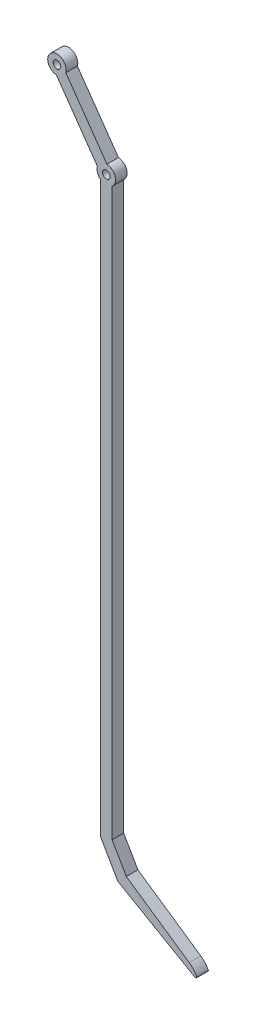
SolidWorks part; units mm, degrees
ref_plane "前视基准面" through (0, 0, 0) normal (0, 0, 1) x (1, 0, 0)
ref_plane "上视基准面" through (0, 0, 0) normal (0, 1, 0) x (1, 0, 0)
ref_plane "右视基准面" through (0, 0, 0) normal (1, 0, 0) x (0, 0, -1)
sketch "草图1" plane through (0, 0, 0) normal (0, 0, 1) x (1, 0, 0)
  line L0 (-2.5, -125) -> (5, -137.9904)
  line L1 (-2.5, 125) -> (2.5, 125) construction
  line L2 (-2.5, 125) -> (-2.5, -125) construction
  line L3 (-2.5, -125) -> (2.5, -125) construction
  line L4 (2.5, 125) -> (2.5, -125) construction
  line L5 (-2.5, 125) -> (2.5, -125) construction
  line L6 (-2.5, -125) -> (2.5, 125) construction
  line L7 (5, -137.9904) -> (9.3301, -135.4904) construction
  line L8 (8.6603, -134.3301) -> (2.5, -123.6603)
  line L9 (2.5, 125) -> (-19.2959, 156.1278)
  line L10 (-19.2959, 156.1278) -> (-23.3917, 153.2599)
  line L11 (-23.3917, 153.2599) -> (-2.5, 123.4235)
  line L12 (-2.5, 123.4235) -> (-2.5, -125)
  line L13 (2.5, -123.6603) -> (2.5, 125)
  line L14 (5, -137.9904) -> (39.641, -157.9904)
  line L15 (39.641, -157.9904) -> (42.141, -153.6603)
  line L16 (42.141, -153.6603) -> (8.6603, -134.3301)
  point P0 (0, 0)
  dimension "D1" = 5
  dimension "D2" = 250
  dimension "D3" = 5
  dimension "D4" = 15
  dimension "D5" = 150
  dimension "D6" = 5
  dimension "D7" = 38
  dimension "D8" = 145
  dimension "D9" = 5
  dimension "D10" = 40
  dimension "D11" = 150
extrude "凸台-拉伸1" add sketch "草图1" along normal blind 5
sketch "草图2" plane through (0, 0, 5) normal (0, 0, 1) x (1, 0, 0)
  line L0 (-2.5, 123.4235) -> (2.5, 125) construction
  line L1 (-19.2959, 156.1278) -> (-23.3917, 153.2599) construction
  circle A0 centre (0, 124.2118) radius 4
  circle A1 centre (-21.3438, 154.6938) radius 4
  dimension "D1" = 8
  dimension "D2" = 8
extrude "凸台-拉伸2" add sketch "草图2" against normal up to surface (5 mm away) up to face at (5.2755, -27.482, 0)
sketch "草图3" plane through (0, 0, 5) normal (0, 0, 1) x (1, 0, 0)
  circle A0 centre (-21.3438, 154.6938) radius 1.65
  circle A1 centre (0, 124.2118) radius 1.65
  dimension "D1" = 3.3
extrude "切除-拉伸1" cut sketch "草图3" against normal blind 5
sketch "草图4" plane through (0, 0, 5) normal (0, 0, 1) x (1, 0, 0)
  line L0 (8.6603, -134.3301) -> (40.641, -156.2583)
  line L1 (39.641, -157.9904) -> (42.141, -153.6603) construction
  line L2 (8.6603, -134.3301) -> (42.141, -153.6603)
  line L3 (42.141, -153.6603) -> (40.641, -156.2583)
  dimension "D1" = 3
extrude "切除-拉伸2" cut sketch "草图4" against normal blind 10
fillet "圆角1" radius 10 1 edges at (40.641, -156.2583, 2.5)
fillet "圆角2" radius 0.5 1 edges at (39.641, -157.9904, 2.5)
